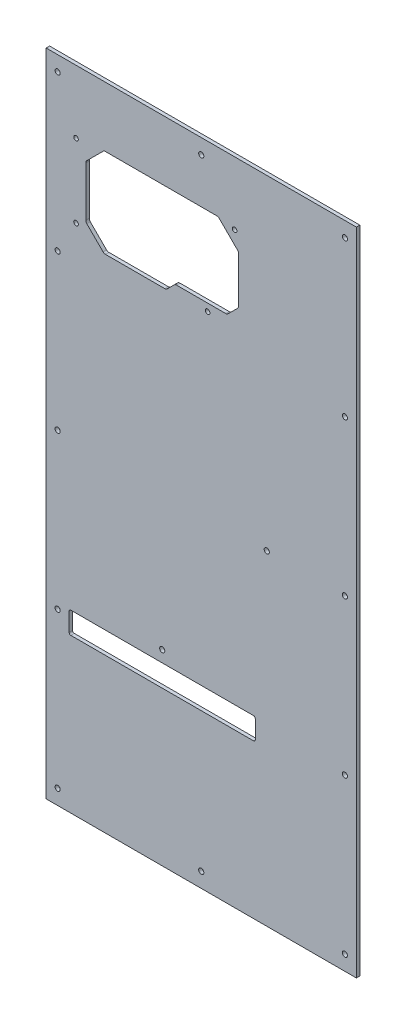
SolidWorks part; units mm, degrees
ref_plane "Спереди" through (0, 0, 0) normal (0, 0, 1) x (1, 0, 0)
ref_plane "Сверху" through (0, 0, 0) normal (0, 1, 0) x (1, 0, 0)
ref_plane "Справа" through (0, 0, 0) normal (1, 0, 0) x (0, 0, -1)
sketch "Эскиз1" plane through (0, 0, 0) normal (0, 0, 1) x (1, 0, 0)
  line L0 (0, 0) -> (270, 0)
  line L1 (0, 0) -> (0, 566)
  line L2 (270, 0) -> (270, 566)
  line L3 (0, 566) -> (270, 566)
  line L4 (10, 553) -> (260, 553) construction
  line L5 (10, 553) -> (10, 13) construction
  line L6 (260, 553) -> (260, 13) construction
  line L7 (10, 13) -> (260, 13) construction
  line L8 (135, 553) -> (135, 13) construction
  circle A0 centre (10, 553) radius 2.25
  circle A1 centre (10, 418) radius 2.25
  circle A2 centre (10, 283) radius 2.25
  circle A3 centre (10, 148) radius 2.25
  circle A4 centre (10, 13) radius 2.25
  circle A5 centre (260, 13) radius 2.25
  circle A6 centre (135, 553) radius 2.25
  circle A7 centre (260, 553) radius 2.25
  circle A8 centre (260, 418) radius 2.25
  circle A9 centre (260, 283) radius 2.25
  circle A10 centre (260, 148) radius 2.25
  circle A11 centre (135, 13) radius 2.25
  dimension "D7" = 4.5
  dimension "D9" = 135
  dimension "D10" = 4.5
  dimension "D12" = 135
  dimension "D13" = 4.5
  dimension "D14" = 4.5
  dimension "D1" = 566
  dimension "D2" = 270
  dimension "D3" = 10
  dimension "D4" = 13
  dimension "D5" = 10
  dimension "D6" = 13
  dimension "D8" = 5
  dimension "D11" = 5
extrude "Бобышка-Вытянуть1" add sketch "Эскиз1" along normal blind 3
sketch "Эскиз2" plane through (0, 0, 0) normal (0, 0, -1) x (-1, 0, 0)
  line L0 (-34.5, 497.8788) -> (-34.5, 452.1212) construction
  line L1 (-50.3712, 513.75) -> (-96.1288, 513.75) construction
  line L2 (-50.3712, 436.25) -> (-96.1288, 436.25) construction
  line L3 (-112, 497.8788) -> (-112, 452.1212) construction
  line L4 (-34.5, 497.8788) -> (-34.5, 452.1212) construction
  line L5 (-50.3712, 513.75) -> (-96.1288, 513.75) construction
  line L6 (-50.3712, 436.25) -> (-96.1288, 436.25) construction
  line L7 (-112, 497.8788) -> (-112, 452.1212) construction
  line L8 (-155.25, 500.5) -> (-124.75, 500.5) construction
  line L9 (-124.75, 475.5) -> (-155.25, 475.5) construction
  line L10 (-155.25, 500.5) -> (-124.75, 500.5) construction
  line L11 (-124.75, 475.5) -> (-155.25, 475.5) construction
  line L16 (-130, 446) -> (-130, 461)
  line L17 (-151, 446) -> (-130, 446)
  line L18 (-151, 461) -> (-151, 446)
  line L19 (-130, 461) -> (-151, 461)
  line L20 (-130, 446) -> (-130, 461) construction
  line L21 (-151, 446) -> (-130, 446) construction
  line L22 (-151, 461) -> (-151, 446) construction
  line L23 (-130, 461) -> (-151, 461) construction
  line L24 (-50.3712, 513.75) -> (-149.75, 513.75)
  line L25 (-149.75, 513.75) -> (-167.5, 496)
  line L26 (-167.5, 496) -> (-167.5, 454)
  line L27 (-157.5, 444) -> (-112.25, 444)
  line L28 (-112.25, 444) -> (-104.5, 436.25)
  line L29 (-104.5, 436.25) -> (-50.3712, 436.25)
  line L30 (-34.5, 452.1212) -> (-34.5, 497.8788)
  line L31 (-167.5, 454) -> (-157.5, 444)
  line L32 (-50.3712, 513.75) -> (-34.5, 497.8788)
  line L33 (-34.5, 452.1212) -> (-50.3712, 436.25)
  arc A0 (-50.3712, 436.25) -> (-34.5, 452.1212) centre (-73.25, 475) ccw construction
  arc A1 (-34.5, 497.8788) -> (-50.3712, 513.75) centre (-73.25, 475) ccw construction
  arc A2 (-112, 452.1212) -> (-96.1288, 436.25) centre (-73.25, 475) ccw construction
  arc A3 (-96.1288, 513.75) -> (-112, 497.8788) centre (-73.25, 475) ccw construction
  arc A4 (-50.3712, 436.25) -> (-34.5, 452.1212) centre (-73.25, 475) ccw construction
  arc A5 (-34.5, 497.8788) -> (-50.3712, 513.75) centre (-73.25, 475) ccw construction
  arc A6 (-112, 452.1212) -> (-96.1288, 436.25) centre (-73.25, 475) ccw construction
  arc A7 (-96.1288, 513.75) -> (-112, 497.8788) centre (-73.25, 475) ccw construction
  arc A8 (-124.75, 475.5) -> (-124.75, 500.5) centre (-127.8878, 488) ccw construction
  arc A9 (-155.25, 500.5) -> (-155.25, 475.5) centre (-152.1122, 488) ccw construction
  arc A10 (-124.75, 475.5) -> (-124.75, 500.5) centre (-127.8878, 488) ccw construction
  arc A11 (-155.25, 500.5) -> (-155.25, 475.5) centre (-152.1122, 488) ccw construction
  circle A12 centre (-164, 511) radius 2.25 construction
  circle A13 centre (-164, 511) radius 2.25 construction
  circle A14 centre (-140.5, 437.5) radius 2.25 construction
  circle A15 centre (-140.5, 437.5) radius 2.25 construction
  circle A16 centre (-26, 447) radius 2.25 construction
  circle A17 centre (-26, 447) radius 2.25 construction
  circle A18 centre (-26, 511) radius 2.25 construction
  circle A19 centre (-26, 511) radius 2.25 construction
  circle A20 centre (-26, 511) radius 2
  circle A21 centre (-26, 447) radius 2
  circle A22 centre (-164, 511) radius 2
  circle A23 centre (-140.5, 437.5) radius 2
  point P35 (-167.5, 444)
  dimension "D8" = 4
  dimension "D9" = 4
  dimension "D10" = 4
  dimension "D11" = 4
  dimension "D2" = 135
  dimension "D3" = 135
  dimension "D4" = 2
  dimension "D5" = 52
  dimension "D6" = 70
  dimension "D7" = 133
  dimension "D12" = 135
  dimension "D13" = 135
  dimension "D1" = 0
extrude "Вырез-Вытянуть1" cut sketch "Эскиз2" against normal through all
sketch "Эскиз3" plane through (0, 0, 0) normal (0, 0, -1) x (-1, 0, 0)
  line L4 (-20, 134) -> (-20, 153)
  line L5 (-182, 134) -> (-20, 134)
  line L6 (-182, 153) -> (-182, 134)
  line L7 (-20, 153) -> (-182, 153)
  line L8 (-20, 134) -> (-20, 153) construction
  line L9 (-182, 134) -> (-20, 134) construction
  line L10 (-182, 153) -> (-182, 134) construction
  line L11 (-20, 153) -> (-182, 153) construction
  line L12 (-20, 153) -> (-182, 153)
  line L13 (-20, 153) -> (-20, 134)
  line L14 (-182, 153) -> (-182, 134)
  line L15 (-20, 134) -> (-182, 134)
  dimension "D2" = 0
  dimension "D3" = 0
  dimension "D4" = 0
  dimension "D5" = 0
  dimension "D1" = 0
extrude "Вырез-Вытянуть2" cut sketch "Эскиз3" against normal through all
sketch "Sketch3" plane through (0, 0, 0) normal (0, 0, -1) x (-1, 0, 0)
  line L0 (-20, 173) -> (-182, 173) construction
  line L1 (-20, 173) -> (-182, 173) construction
  line L2 (-202, 23) -> (-202, 543) construction
  line L3 (-202, 23) -> (-202, 543) construction
  line L5 (-101, 153) -> (-101, 178.2817) construction
  line L6 (-20, 153) -> (-182, 153) construction
  line L7 (-202, 283) -> (-180.285, 283) construction
  circle A0 centre (-101, 163) radius 2.25
  circle A1 centre (-192, 283) radius 2.25
  dimension "D1" = 4.5
  dimension "D3" = 4.5
  dimension "D4" = 10
  dimension "D2" = 10
extrude "Cut-Extrude1" cut sketch "Sketch3" against normal through all
fillet "Fillet1" radius 3 10 edges at (50.3712, 513.75, 1.5) (34.5, 497.8788, 1.5) (34.5, 452.1212, 1.5) (50.3712, 436.25, 1.5) (104.5, 436.25, 1.5) (112.25, 444, 1.5) (157.5, 444, 1.5) (167.5, 454, 1.5) (167.5, 496, 1.5) (149.75, 513.75, 1.5)
fillet "Fillet2" radius 1.5 4 edges at (20, 134, 1.5) (20, 153, 1.5) (182, 134, 1.5) (182, 153, 1.5)
